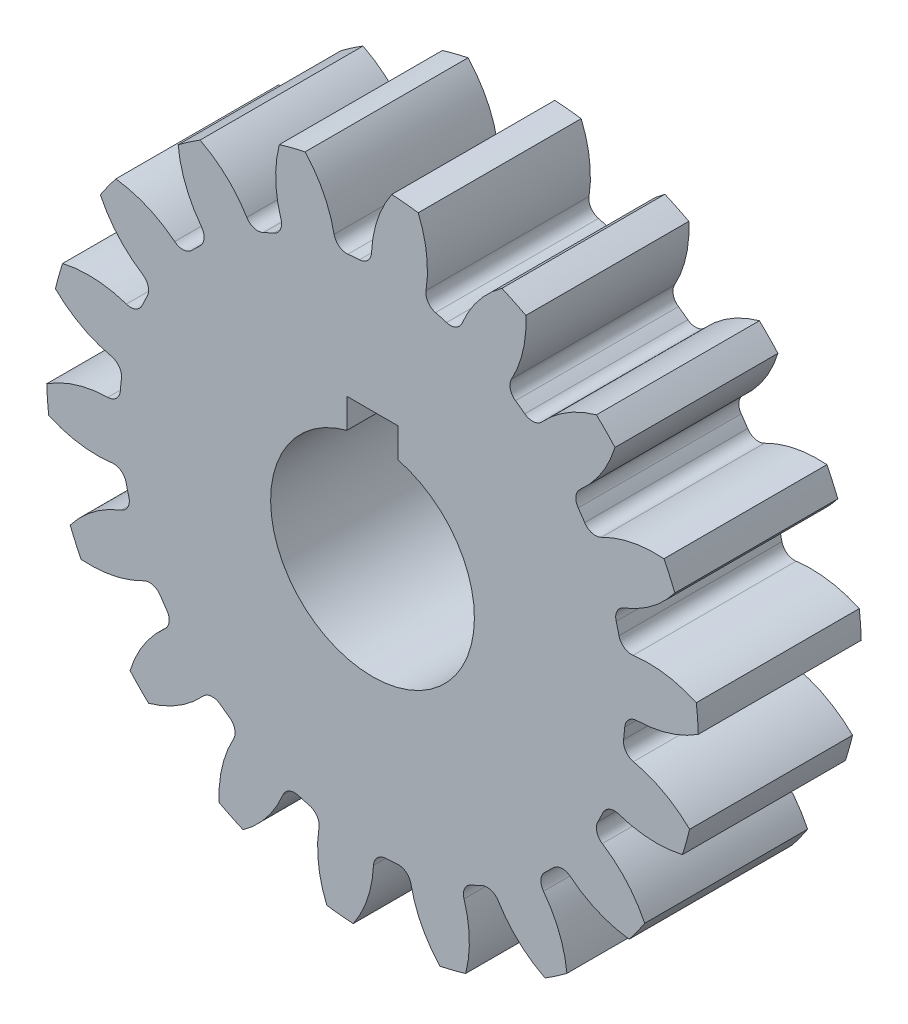
SolidWorks part; units mm, degrees
ref_plane "Front" through (0, 0, 0) normal (0, 0, 1) x (1, 0, 0)
ref_plane "Top" through (0, 0, 0) normal (0, 1, 0) x (1, 0, 0)
ref_plane "Right" through (0, 0, 0) normal (1, 0, 0) x (0, 0, -1)
sketch "Sketch3" plane through (0, 0, 0) normal (0, 0, 1) x (1, 0, 0)
  circle A0 centre (0, 0) radius 12.7
  dimension "od" = 25.4
extrude "gearBody" add sketch "Sketch3" along normal blind 6.35
sketch "Sketch2" plane through (0, 0, 0) normal (0, 0, 1) x (1, 0, 0)
  line L0 (0, 0) -> (10.2236, 4.2347) construction
  line L1 (13.3591, -4.4187) -> (0, 0) construction
  line L2 (0, 0) -> (36.3143, 0) construction
  line L3 (11.4292, -0.1374) -> (11.2291, -2.1338) construction
  line L5 (11.3291, -1.1356) -> (0, 0) construction
  line L7 (0, 0) -> (11.0659, 0) construction
  arc A0 (11.0637, -0.2221) -> (10.8877, -1.9783) centre (0, 0) ccw construction
  arc A1 (12.6927, 0.4305) -> (12.3547, -2.9412) centre (0, 0) ccw construction
  arc A2 (11.4292, -0.1374) -> (11.2291, -2.1338) centre (0, 0) ccw construction
  arc A3 (9.7812, -1.2052) -> (9.8258, -0.7602) centre (0, 0) ccw
  arc A4 (13.3591, -4.4187) -> (10.1678, -1.7534) centre (9.1796, -6.1797) ccw
  arc A5 (13.3591, -4.4187) -> (13.9704, 1.6792) centre (0, 0) ccw
  arc A6 (13.9704, 1.6792) -> (10.3136, -0.2997) centre (10.2236, 4.2347) cw
  arc A7 (9.8258, -0.7602) -> (10.3136, -0.2997) centre (10.3235, -0.7987) cw
  arc A8 (10.1678, -1.7534) -> (9.7812, -1.2052) centre (10.2766, -1.2662) cw
  point P6 (13.9704, 1.6792)
  point P22 (13.3591, -4.4187)
  dimension "baseDia" = 22.1319
  dimension "od" = 25.4
  dimension "pd" = 22.86
  dimension "rd" = 19.7104
  dimension "rFillet" = 0.4991
  dimension "pointX" = 13.9704
  dimension "pointY" = 1.6792
  dimension "CTT" = 1.9964
  dimension "flankCenterAngle" = 22.5
extrude "toothCut" cut sketch "Sketch2" along normal through all
pattern_circular "CirPattern1" count 18 over 360 about axis through (0, 0, 6.35) along (0, 0, -1) of "toothCut"
sketch "hub1Dia" plane through (0, 0, 0) normal (0, 0, -1) x (-1, 0, 0)
  circle A0 centre (0, 0) radius 25.4
  dimension "hub1Dia" = 50.8
extrude "hub1" [suppressed] add sketch "hub1Dia" along normal blind 19.05
sketch "hub2Dia" plane through (0, 0, 6.35) normal (0, 0, 1) x (1, 0, 0)
  circle A0 centre (0, 0) radius 21.844
  dimension "hub2dia" = 43.688
extrude "hub2" [suppressed] add sketch "hub2Dia" along normal blind 16.002
sketch "boreDia" plane through (0, 0, 0) normal (0, 0, 1) x (1, 0, 0)
  line L1 (-1, 3.842) -> (-1, 4.9926)
  line L2 (1, 3.842) -> (1, 4.9926)
  line L3 (-1, 4.9926) -> (1, 4.9926)
  arc A0 (-1, 3.842) -> (1, 3.842) centre (0, 0) ccw
  dimension "D1" = 2
  dimension "boreDia" = 7.94
  dimension "D2" = 1.1506
extrude "bore" cut sketch "boreDia" against normal mid plane 25400
chamfer "hub2Chamfer" [suppressed] distance 0.508 angle 45
chamfer "hub2BoreChamfer" [suppressed] distance 0.508 angle 45
chamfer "hub1BoreChamfer" [suppressed] distance 0.508 angle 45
chamfer "hub1Chamfer" [suppressed] distance 0.508 angle 45
chamfer "BoreChamfer2" [suppressed] distance 0.508 angle 45
chamfer "boreChamfer1" [suppressed] distance 0.508 angle 45
